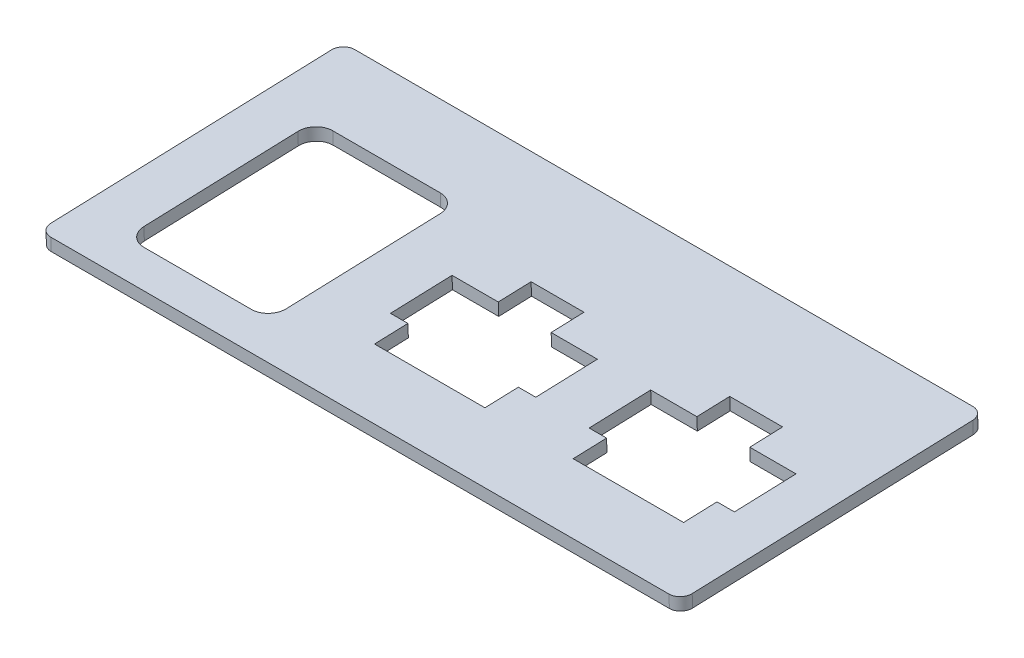
SolidWorks part; units mm, degrees
ref_plane "Front Plane" through (0, 0, 0) normal (0, 0, 1) x (1, 0, 0)
ref_plane "Top Plane" through (0, 0, 0) normal (0, 1, 0) x (1, 0, 0)
ref_plane "Right Plane" through (0, 0, 0) normal (1, 0, 0) x (0, 0, -1)
sketch "Sketch1" plane through (0, -71.9872, -2.5138) normal (0, 0.9994, 0.0349) x (1, 0, 0)
  line L0 (-56.175, 48.6398) -> (56.175, 48.6398) construction
  line L1 (-52.175, -2.9116) -> (-56.175, -2.9116) construction
  line L8 (-55.175, -4.4116) -> (55.175, -4.4116)
  line L9 (55.175, -4.4116) -> (55.175, 47.8898)
  line L10 (55.175, 47.8898) -> (-55.175, 47.8898)
  line L11 (-55.175, 47.8898) -> (-55.175, -4.4116)
  dimension "D4" = 0.75
  dimension "D1" = 1.5
  dimension "D2" = 3.0034
  dimension "D3" = 3.0034
extrude "Boss-Extrude1" add sketch "Sketch1" along normal blind 2.2
sketch "Sketch2" plane through (0, -71.9872, -2.5138) normal (0, -0.9994, -0.0349) x (1, 0, 0)
  line L0 (-4.05, -23.4641) -> (-4.05, -29.1141)
  line L1 (-43.425, -1.8641) -> (-24.925, -1.8641)
  line L2 (-46.425, -4.8641) -> (-46.425, -31.3641)
  line L3 (-43.425, -34.3641) -> (-24.925, -34.3641)
  line L4 (-21.925, -4.8641) -> (-21.925, -31.3641)
  line L5 (-12, -12.8641) -> (-9, -12.8641)
  line L6 (-12, -12.8641) -> (-12, -23.4641)
  line L7 (-12, -23.4641) -> (-4.05, -23.4641)
  line L8 (13, -12.8641) -> (13, -23.4641)
  line L9 (-9, -7.1141) -> (10, -7.1141)
  line L10 (-9, -7.1141) -> (-9, -12.8641)
  line L11 (-4.05, -29.1141) -> (5.05, -29.1141)
  line L12 (10, -7.1141) -> (10, -12.8641)
  line L13 (10, -12.8641) -> (13, -12.8641)
  line L14 (5.05, -23.4641) -> (5.05, -29.1141)
  line L15 (5.05, -23.4641) -> (13, -23.4641)
  line L16 (-13, -4.6141) -> (14, -31.6141) construction
  line L17 (-13, -4.6141) -> (14, -4.6141) construction
  line L18 (-13, -4.6141) -> (-13, -31.6141) construction
  line L19 (-13, -31.6141) -> (14, -31.6141) construction
  line L20 (14, -4.6141) -> (14, -31.6141) construction
  line L21 (17.5875, 3.7502) -> (17.5875, -36.664) construction
  line L22 (47.175, -18.1641) -> (22.175, -18.1641) construction
  line L23 (34.675, -7.1141) -> (34.675, -29.1141) construction
  line L24 (21.175, -4.6141) -> (21.175, -31.6141) construction
  line L25 (48.175, -31.6141) -> (21.175, -31.6141) construction
  line L26 (48.175, -4.6141) -> (48.175, -31.6141) construction
  line L27 (48.175, -4.6141) -> (21.175, -4.6141) construction
  line L28 (-48.175, -18.1141) -> (-46.425, -18.1141) construction
  line L29 (-48.175, -0.1141) -> (-20.175, -0.1141) construction
  line L30 (-48.175, -0.1141) -> (-48.175, -36.1141) construction
  line L31 (-48.175, -36.1141) -> (-20.175, -36.1141) construction
  line L32 (-20.175, -0.1141) -> (-20.175, -36.1141) construction
  line L33 (-34.175, -1.8641) -> (-34.175, -0.1141) construction
  line L34 (0.5, -7.1141) -> (0.5, -29.1141) construction
  line L35 (-12, -18.1641) -> (13, -18.1641) construction
  line L36 (48.175, -4.6141) -> (21.175, -31.6141) construction
  line L37 (30.125, -23.4641) -> (22.175, -23.4641)
  line L38 (30.125, -23.4641) -> (30.125, -29.1141)
  line L39 (25.175, -12.8641) -> (22.175, -12.8641)
  line L40 (25.175, -7.1141) -> (25.175, -12.8641)
  line L41 (39.225, -29.1141) -> (30.125, -29.1141)
  line L42 (44.175, -7.1141) -> (44.175, -12.8641)
  line L43 (44.175, -7.1141) -> (25.175, -7.1141)
  line L44 (22.175, -12.8641) -> (22.175, -23.4641)
  line L45 (47.175, -23.4641) -> (39.225, -23.4641)
  line L46 (47.175, -12.8641) -> (47.175, -23.4641)
  line L47 (47.175, -12.8641) -> (44.175, -12.8641)
  line L48 (39.225, -23.4641) -> (39.225, -29.1141)
  line L49 (21.175, -18.1141) -> (14, -18.1141) construction
  line L50 (-55.175, 4.4116) -> (55.175, 4.4116) construction
  line L51 (48.175, -18.1141) -> (52.175, -18.1141) construction
  line L52 (55.175, 4.4116) -> (55.175, -47.8898) construction
  line L53 (-46.7914, -40.6398) -> (46.7914, -40.6398) construction
  line L54 (-13, -18.1141) -> (-20.175, -18.1141) construction
  line L55 (-34.175, -0.1141) -> (-34.175, 4.4116) construction
  line L56 (-34.175, -36.1141) -> (-34.175, -40.6398) construction
  line L57 (-55.175, -47.8898) -> (-55.175, 4.4116) construction
  line L58 (-48.175, -18.1141) -> (-52.175, -18.1141) construction
  arc A0 (-46.425, -31.3641) -> (-43.425, -34.3641) centre (-43.425, -31.3641) ccw
  arc A1 (-24.925, -34.3641) -> (-21.925, -31.3641) centre (-24.925, -31.3641) ccw
  arc A2 (-24.925, -1.8641) -> (-21.925, -4.8641) centre (-24.925, -4.8641) cw
  arc A3 (-43.425, -1.8641) -> (-46.425, -4.8641) centre (-43.425, -4.8641) ccw
  point P28 (0.5, -18.1141)
  point P63 (34.675, -18.1141)
  dimension "D1" = 3
  dimension "D2" = 32.5
  dimension "D3" = 24.5
  dimension "D4" = 28
  dimension "D5" = 36
  dimension "D6" = 25
  dimension "D7" = 22
  dimension "D8" = 10.6
  dimension "D9" = 19
  dimension "D10" = 9.1
  dimension "D11" = 5.75
  dimension "D12" = 27
  dimension "D13" = 27
  dimension "D14" = 4
  dimension "D15" = 3
  dimension "D16" = 3
extrude "Cut-Extrude1" cut sketch "Sketch2" against normal up to next
fillet "Fillet1" radius 2 4 edges at (-55.175, -71.0418, 1.9334) (55.175, -71.0418, 1.9334) (55.175, -69.2165, -50.336) (-55.175, -69.2165, -50.336)
